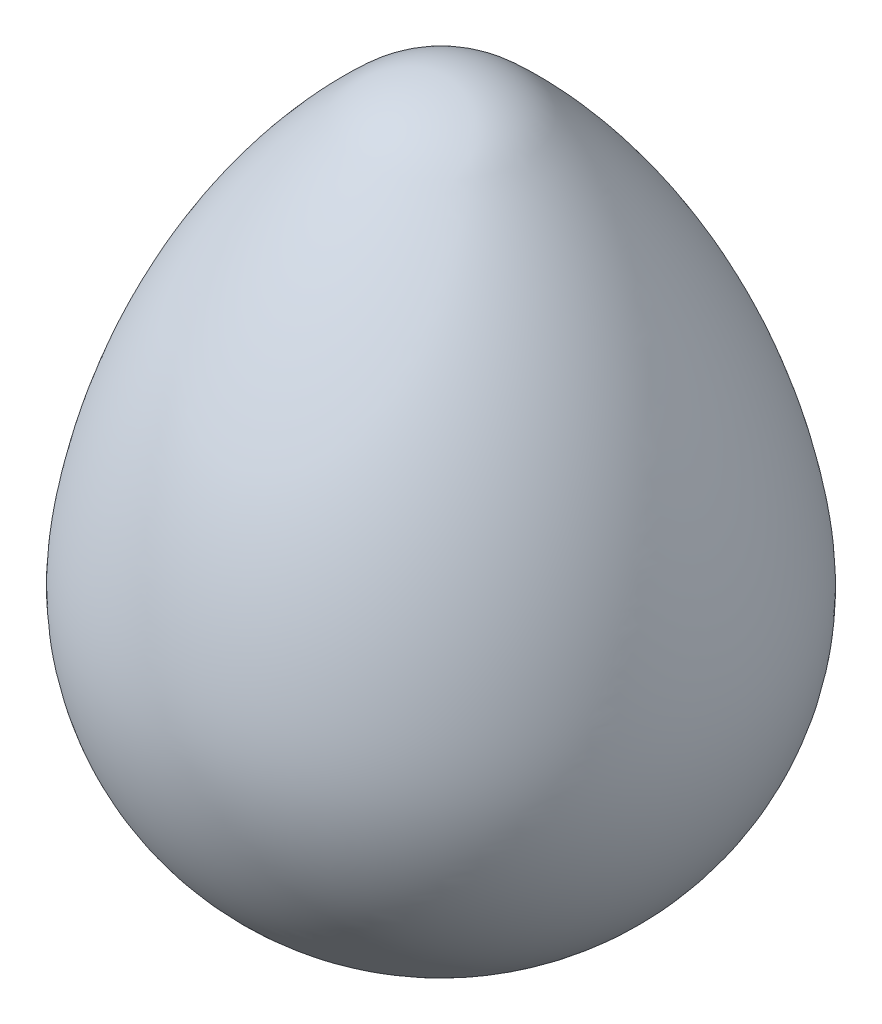
SolidWorks part; units mm, degrees
ref_plane "Front Plane" through (0, 0, 0) normal (0, 0, 1) x (1, 0, 0)
ref_plane "Top Plane" through (0, 0, 0) normal (0, 1, 0) x (1, 0, 0)
ref_plane "Right Plane" through (0, 0, 0) normal (1, 0, 0) x (0, 0, -1)
sketch "Sketch1" plane through (0, 0, 0) normal (0, 0, 1) x (1, 0, 0)
  line L15 (0, 27.5) -> (0, -17.5)
  line L16 (0, 0) -> (0, 35.011) construction
  arc A0 (0, -17.5) -> (17.2472, 2.9641) centre (0, 0) ccw construction
  arc A1 (17.2472, 2.9641) -> (5, 25.5408) centre (-22.1749, -3.8109) ccw construction
  arc A2 (5, 25.5408) -> (0, 27.5) centre (0, 20.1403) ccw construction
  spline S0 degree 3 poles (0, 27.5) (1.3925, 27.5) (2.7308, 27.115) (3.9105, 26.3751) (4.1686, 26.2133) (4.6647, 25.8575) (5.338, 25.229) (5.7755, 24.8049) (5.9919, 24.5903) (10.346, 20.2722) (13.6115, 15.0818) (15.6196, 9.2876) (16.1265, 7.8252) (16.9704, 4.8415) (17.7089, 0.0044) (17.2943, -3.0906) (16.8889, -4.5843) (14.7373, -12.5107) (8.2132, -17.5) (0, -17.5) knots 0 0 0 0 0.067726 0.067726 0.067726 0.082937 0.098149 0.11336 0.11336 0.11336 0.414275 0.414275 0.414275 0.491558 0.568841 0.646124 0.646124 0.646124 1 1 1 1 weights 1 0.97402 0.97402 1 1 1 1 1 1 0.982753 0.982753 1 1 1 1 1 1 0.862895 0.862895 1
  point P9 (0, 0)
  point P10 (11.52, 21.3738)
  point P11 (0, 0)
  point P12 (18.274, 8.1278)
  point P13 (12.5701, 18.3588)
  point P14 (0, 0)
  point P15 (0, 0)
  point P16 (16.9795, -4.2363)
  point P17 (17.1114, 3.6674)
  dimension "D1" = 35
  dimension "D2" = 45
  dimension "D4" = 40
  dimension "D3" = 10
revolve "Revolve1" add sketch "Sketch1" angle 360 about L16
